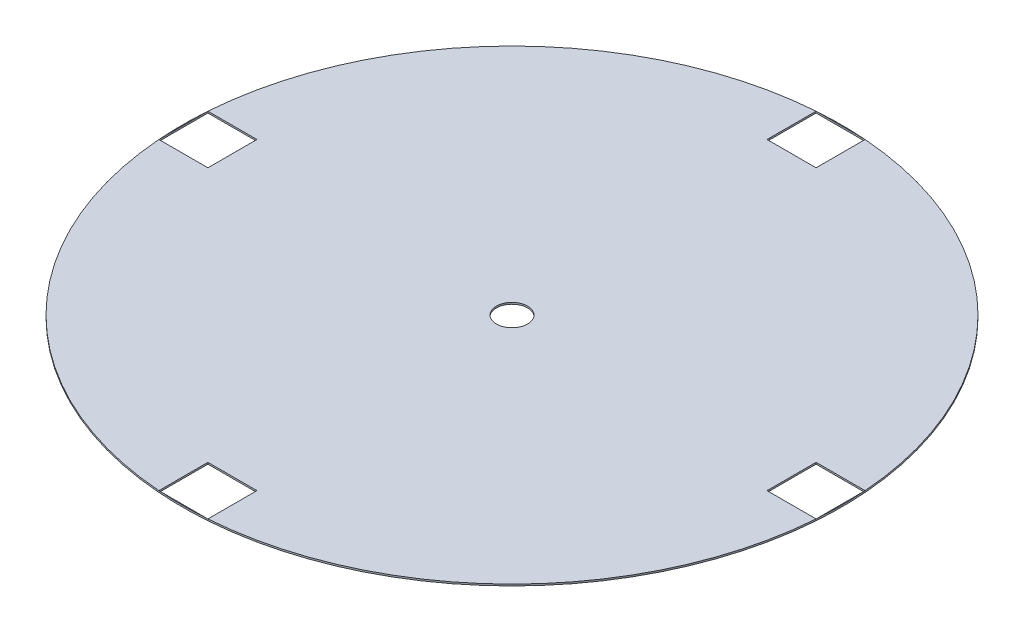
SolidWorks part; units mm, degrees
ref_plane "Alzado" through (0, 0, 0) normal (0, 0, 1) x (1, 0, 0)
ref_plane "Planta" through (0, 0, 0) normal (0, 1, 0) x (1, 0, 0)
ref_plane "Vista lateral" through (0, 0, 0) normal (1, 0, 0) x (0, 0, -1)
sketch "Croquis1" plane through (0, 0, 0) normal (0, 1, 0) x (1, 0, 0)
  circle A0 centre (0, 0) radius 403.28
  circle A1 centre (0, 0) radius 19.05
  dimension "D1" = 38.1
  dimension "D2" = 806.56
extrude "Saliente-Extruir1" add sketch "Croquis1" along normal blind 2
sketch "Croquis2" plane through (0, 2, 0) normal (0, 1, 0) x (1, 0, 0)
  line L0 (402.1626, 30) -> (317.3098, 30)
  line L1 (317.3098, 30) -> (317.3098, -30)
  line L2 (317.3098, -30) -> (402.1626, -30)
  line L3 (402.1626, -30) -> (402.1626, 30)
  line L4 (0, 0) -> (317.3098, 0) construction
  line L5 (30, -402.1626) -> (30, -317.3098)
  line L6 (30, -317.3098) -> (-30, -317.3098)
  line L7 (-30, -317.3098) -> (-30, -402.1626)
  line L8 (-30, -402.1626) -> (30, -402.1626)
  line L9 (-402.1626, -30) -> (-317.3098, -30)
  line L10 (-317.3098, -30) -> (-317.3098, 30)
  line L11 (-317.3098, 30) -> (-402.1626, 30)
  line L12 (-402.1626, 30) -> (-402.1626, -30)
  line L13 (-30, 402.1626) -> (-30, 317.3098)
  line L14 (-30, 317.3098) -> (30, 317.3098)
  line L15 (30, 317.3098) -> (30, 402.1626)
  line L16 (30, 402.1626) -> (-30, 402.1626)
  line L17 (0, 0) -> (0, 317.3098) construction
  line L18 (0, 0) -> (-317.3098, 0) construction
  line L19 (0, 0) -> (0, -317.3098) construction
  circle A0 centre (0, 0) radius 403.28 construction
  point P10 (402.1626, 0)
  point P19 (0, -402.1626)
  point P24 (-402.1626, 0)
  point P29 (0, 402.1626)
  point P30 (0, 0)
  dimension "D1" = 84.8528
  dimension "D2" = 60
  dimension "D3" = 4
sketch "Croquis3" plane through (0, 2, 0) normal (0, 1, 0) x (1, 0, 0)
  line L0 (402.1626, 30) -> (342.1626, 30)
  line L1 (342.1626, 30) -> (342.1626, -30)
  line L2 (342.1626, -30) -> (402.1626, -30)
  line L3 (402.1626, -30) -> (402.1626, 30)
  line L4 (0, 0) -> (342.1626, 0) construction
  line L19 (30, -402.1626) -> (30, -342.1626)
  line L20 (30, -342.1626) -> (-30, -342.1626)
  line L21 (-30, -342.1626) -> (-30, -402.1626)
  line L22 (-30, -402.1626) -> (30, -402.1626)
  line L23 (0, 0) -> (0, -342.1626) construction
  line L24 (-402.1626, -30) -> (-342.1626, -30)
  line L25 (-342.1626, -30) -> (-342.1626, 30)
  line L26 (-342.1626, 30) -> (-402.1626, 30)
  line L27 (-402.1626, 30) -> (-402.1626, -30)
  line L28 (0, 0) -> (-342.1626, 0) construction
  line L29 (-30, 402.1626) -> (-30, 342.1626)
  line L30 (-30, 342.1626) -> (30, 342.1626)
  line L31 (30, 342.1626) -> (30, 402.1626)
  line L32 (30, 402.1626) -> (-30, 402.1626)
  line L33 (0, 0) -> (0, 342.1626) construction
  circle A2 centre (0, 0) radius 403.28 construction
  point P6 (0, 0)
  point P8 (402.1626, 0)
  point P19 (0, -402.1626)
  point P25 (-402.1626, 0)
  point P34 (0, 402.1626)
  point P35 (0, 0)
  dimension "D1" = 806.56
  dimension "D2" = 60
  dimension "D3" = 4
  dimension "D4" = 60
extrude "Cortar-Extruir1" cut sketch "Croquis3" against normal through all
